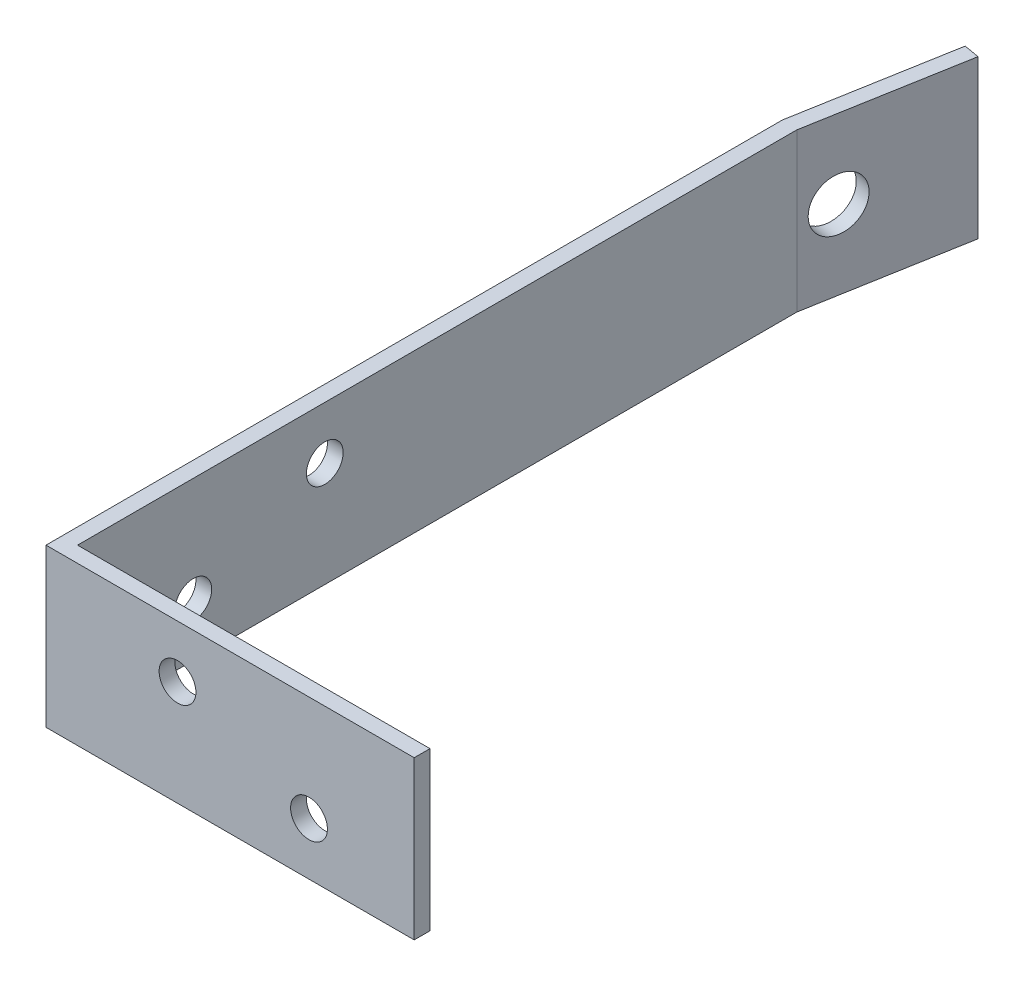
SolidWorks part; units mm, degrees
ref_plane "Спереди" through (0, 0, 0) normal (0, 0, 1) x (1, 0, 0)
ref_plane "Сверху" through (0, 0, 0) normal (0, 1, 0) x (1, 0, 0)
ref_plane "Справа" through (0, 0, 0) normal (1, 0, 0) x (0, 0, -1)
sketch "Эскиз1" plane through (0, 0, 0) normal (0, 1, 0) x (1, 0, 0)
  line L0 (0, 0) -> (70, 0)
  line L1 (0, 0) -> (0, 140)
  line L2 (0, 140) -> (5.2094, 169.5442)
extrude "Вытянуть-Тонкостенный1" add sketch "Эскиз1" along normal blind 30 thin thin type one direction wall 3
sketch "Эскиз2" plane through (0, 0, 0) normal (-1, 0, 0) x (0, 0, 1)
  circle A1 centre (-50, 20) radius 3.5
  circle A2 centre (-25, 10) radius 3.5
  point P6 (0, 0)
extrude "Вырез-Вытянуть1" cut sketch "Эскиз2" against normal through all
sketch "Эскиз3" plane through (0, 0, 0) normal (0, 0, 1) x (1, 0, 0)
  circle A0 centre (25, 20) radius 3.5
  circle A1 centre (50, 10) radius 3.5
extrude "Вырез-Вытянуть2" cut sketch "Эскиз3" against normal through all
sketch "Эскиз4" plane through (-23.9414, 0, -4.2215) normal (-0.9848, 0, -0.1736) x (-0.1736, 0, 0.9848)
  circle A0 centre (-145, 15) radius 5
extrude "Вырез-Вытянуть3" cut sketch "Эскиз4" against normal through all
